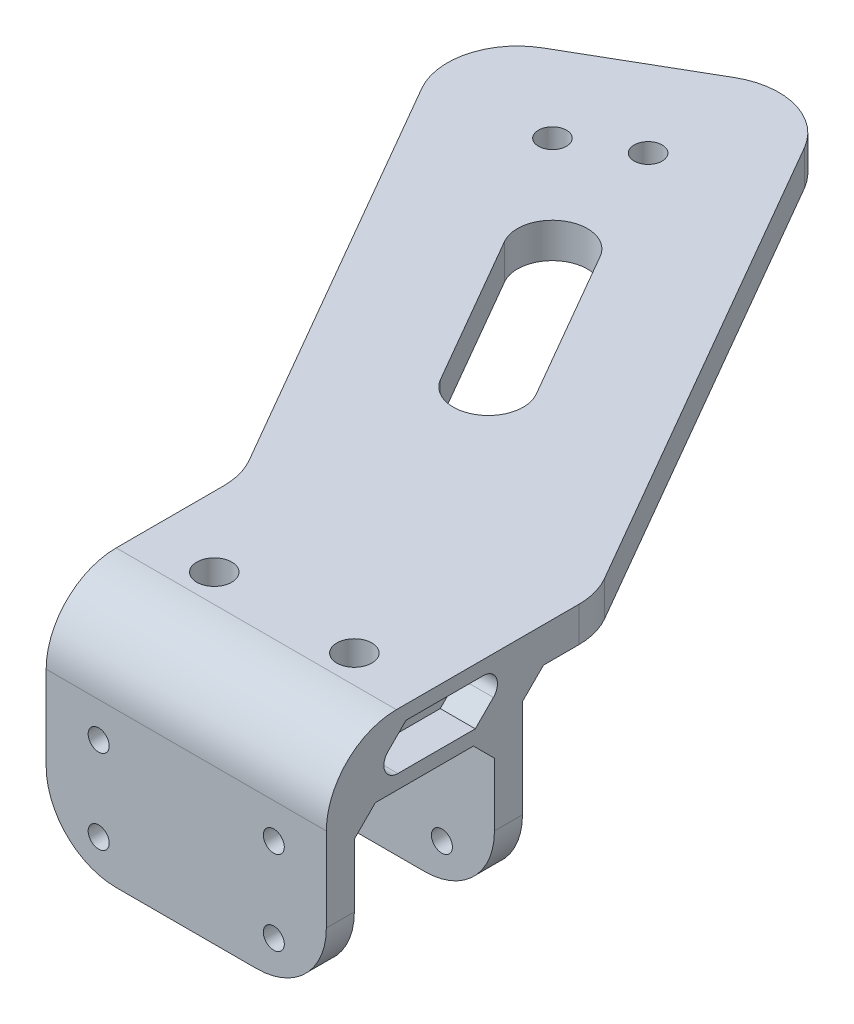
SolidWorks part; units mm, degrees
ref_plane "前视基准面" through (0, 0, 0) normal (0, 0, 1) x (1, 0, 0)
ref_plane "上视基准面" through (0, 0, 0) normal (0, 1, 0) x (1, 0, 0)
ref_plane "右视基准面" through (0, 0, 0) normal (1, 0, 0) x (0, 0, -1)
other "Configuration Table"
sketch "草图1" plane through (0, 0, 0) normal (0, 1, 0) x (1, 0, 0)
  line L1 (20, 14) -> (-20, 14)
  line L2 (20, 14) -> (20, -14)
  line L3 (20, -14) -> (-20, -14)
  line L4 (-20, 14) -> (-20, -14)
  line L5 (20, 14) -> (-20, -14) construction
  line L6 (20, -14) -> (-20, 14) construction
  point P0 (0, 0)
  dimension "D1" = 28
  dimension "D2" = 40
extrude "凸台-拉伸1" add sketch "草图1" along normal blind 10
sketch "草图2" plane through (0, 0, 0) normal (0, -1, 0) x (1, 0, 0)
  line L0 (20, 14) -> (20, -14) construction
  line L1 (-20, 14) -> (20, 14)
  line L2 (-20, 14) -> (-20, 10)
  line L3 (-20, 10) -> (20, 10)
  line L4 (20, 14) -> (20, 10)
  line L5 (-20, -14) -> (-20, 14) construction
  line L6 (-20, -10) -> (20, -10)
  line L7 (-20, -10) -> (-20, -14)
  line L8 (-20, -14) -> (20, -14)
  line L9 (20, -10) -> (20, -14)
  dimension "D1" = 4
  dimension "D2" = 4
extrude "凸台-拉伸2" add sketch "草图2" along normal blind 10
sketch "草图4" plane through (0, 0, -14) normal (0, 0, -1) x (-1, 0, 0)
  line L1 (20, 10) -> (20, -10) construction
  line L2 (-20, 10) -> (20, 10)
  line L3 (-20, 10) -> (-20, 5)
  line L4 (-20, 5) -> (20, 5)
  line L5 (20, 10) -> (20, 5)
  dimension "D1" = 5
extrude "凸台-拉伸3" add sketch "草图4" along normal blind 15
sketch "草图6" plane through (0, 0, -29) normal (0, 0, -1) x (-1, 0, 0)
  line L4 (-20, 10) -> (-20, 5)
  line L5 (-20, 5) -> (20, 5)
  line L6 (20, 5) -> (20, 10)
  line L7 (20, 10) -> (-20, 10)
  line L8 (-20, 10) -> (-20, 5)
  line L9 (-20, 5) -> (20, 5)
  line L10 (20, 5) -> (20, 10)
  line L11 (20, 10) -> (-20, 10)
  dimension "D1" = 0
extrude "凸台-拉伸4" add sketch "草图6" along normal blind 15
sketch "草图7" plane through (0, 5, 0) normal (0, -1, 0) x (1, 0, 0)
  line L0 (0, -39) -> (0, -24) construction
  line L1 (-3.15, -39) -> (-3.15, -24)
  line L2 (3.15, -39) -> (3.15, -24)
  line L3 (20, -44) -> (-20, -44) construction
  arc A0 (-3.15, -39) -> (3.15, -39) centre (0, -39) ccw
  arc A1 (3.15, -24) -> (-3.15, -24) centre (0, -24) ccw
  point P2 (0, -31.5)
  dimension "D1" = 6.3
  dimension "D2" = 15
  dimension "D3" = 5
sketch "草图8" plane through (0, 10, 0) normal (0, 1, 0) x (1, 0, 0)
  line L0 (-20, -14) -> (20, -14) construction
  line L1 (20, -14) -> (20, 44) construction
  line L2 (-20, 44) -> (-20, -14) construction
  circle A0 centre (-10, 0) radius 2.5
  circle A1 centre (10, 0) radius 2.5
  dimension "D1" = 5
  dimension "D3" = 14
  dimension "D4" = 10
  dimension "D5" = 10
  dimension "D2" = 14
extrude "切除-拉伸2" cut sketch "草图8" against normal blind 15
chamfer "倒角1" distance 3 angle 45 2 edges at (0, 0, 10) (0, 0, -10)
fillet "圆角1" radius 10 1 edges at (0, 10, 14)
chamfer "倒角2" distance 3 angle 45 1 edges at (0, 5, -14)
sketch "草图9" plane through (0, 0, -14) normal (0, 0, -1) x (-1, 0, 0)
  line L0 (20, -10) -> (-20, -10) construction
  line L1 (20, 2) -> (20, -10) construction
  line L2 (-20, 2) -> (-20, -10) construction
  circle A0 centre (-12.5, -5) radius 1.5
  circle A1 centre (12.5, -5) radius 1.5
  dimension "D1" = 5
  dimension "D2" = 5
  dimension "D3" = 7.5
  dimension "D4" = 7.5
  dimension "D5" = 3
extrude "切除-拉伸3" cut sketch "草图9" against normal through all
sketch "草图10" plane through (20, 0, 0) normal (1, 0, 0) x (0, 0, -1)
  line L0 (-2.6185, 8) -> (-8.6185, 2)
  line L1 (-8.6185, 2) -> (7.2641, 2)
  line L2 (7.2641, 2) -> (13.2641, 8)
  line L3 (13.2641, 8) -> (-2.6185, 8)
  line L4 (-7, 0) -> (7, 0) construction
  line L5 (-4, 10) -> (44, 10) construction
  line L6 (-10, -3) -> (-7, 0) construction
  dimension "D1" = 2
  dimension "D2" = 2
extrude "切除-拉伸4" cut sketch "草图10" against normal blind 5
fillet "圆角3" radius 2 2 edges at (17.5, 8, -13.2641) (17.5, 2, 8.6185)
ref_plane "基准面1" through (0, 0, 0) normal (1, 0, 0) x (0, 0, -1)
mirror "镜向1" about plane through (0, 0, 0) normal (1, 0, 0) of "切除-拉伸4"
sketch "草图11" plane through (0, -10, 0) normal (0, -1, 0) x (1, 0, 0)
  line L0 (20, 14) -> (-20, 14) construction
  line L1 (-20, -14) -> (20, -14)
  line L2 (-20, -14) -> (-20, -7)
  line L3 (-20, -7) -> (20, -7)
  line L4 (20, -14) -> (20, -7)
  line L5 (-20, 14) -> (20, 14)
  line L6 (-20, 14) -> (-20, 7)
  line L7 (-20, 7) -> (20, 7)
  line L8 (20, 14) -> (20, 7)
  dimension "D1" = 7
  dimension "D2" = 7
extrude "凸台-拉伸5" add sketch "草图11" against normal blind 3 contours L2 L1 L4 L3 | L6 L5 L8 L7
chamfer "倒角3" distance 1 angle 45 2 edges at (0, -7, -7) (0, -7, 7)
sketch "草图12" plane through (0, 0, -44) normal (0, 0, -1) x (-1, 0, 0)
  line L1 (-20, 10) -> (20, 10)
  line L2 (-20, 10) -> (-20, 5)
  line L3 (-20, 5) -> (20, 5)
  line L4 (20, 10) -> (20, 5)
extrude "凸台-拉伸6" add sketch "草图12" along normal blind 30
fillet "圆角4" radius 10 2 edges at (-20, 7.5, -74) (20, 7.5, -74)
sketch "草图13" plane through (0, 10, 0) normal (0, 1, 0) x (1, 0, 0)
  line L0 (20, -4) -> (20, 64) construction
  line L1 (-10, 74) -> (10, 74) construction
  circle A0 centre (9.14, 70) radius 2
  circle A1 centre (-0.86, 70) radius 2
  dimension "D1" = 4
  dimension "D2" = 10.86
  dimension "D3" = 10
  dimension "D4" = 4
  dimension "D5" = 4
extrude "切除-拉伸5" cut sketch "草图13" against normal blind 30
sketch "草图14" plane through (0, 10, 0) normal (0, 1, 0) x (1, 0, 0)
  line L0 (-20, 14) -> (-73.9448, 14) construction
  line L1 (-20, 14) -> (-55, 74.6218)
  line L2 (-20.359, 94.6218) -> (-55, 74.6218)
  line L3 (-20.359, 94.6218) -> (20, 24.718)
  line L4 (-20, 14) -> (-20, 7)
  line L5 (20, 14) -> (-20, 14)
  line L6 (20, 7) -> (20, 14)
  line L7 (-20, 7) -> (20, 7)
  line L8 (-20, 14) -> (-20, 7)
  line L9 (20, 14) -> (-20, 14)
  line L10 (20, 7) -> (20, 14)
  line L11 (-20, 7) -> (20, 7)
  line L12 (20, -4) -> (20, 64) construction
  line L13 (20, 24.718) -> (20, 14)
  line M13 (10, 74) -> (-10, 74)
  arc M14 (-10, 74) -> (-20, 64) centre (-10, 64) ccw
  line M15 (-20, 64) -> (-20, -4)
  line M17 (20, -4) -> (20, 64)
  dimension "D2" = 60
  dimension "D3" = 40
  dimension "D4" = 90
  dimension "D5" = 70
  dimension "D1" = 0
extrude "凸台-拉伸7" add sketch "草图14" against normal blind 5 contours L9 L3 M17 M13 M14 M15 | L3 L2 L1 M15 M14 M13 region at (-4.1679, 10, -37.9718) region at (-30.3206, 10, -62.7466)
sketch "草图15" plane through (0, 10, 0) normal (0, 1, 0) x (1, 0, 0)
  line L0 (-8.453, 74) -> (20, 24.718)
  line L1 (20, -4) -> (20, 64) construction
  line L2 (20, 24.718) -> (20, 77.5211)
  line L3 (20, 77.5211) -> (-8.453, 74)
extrude "切除-拉伸6" cut sketch "草图15" against normal blind 5
sketch "草图16" plane through (20, 0, 0) normal (1, 0, 0) x (0, 0, -1)
  line L1 (-10, -7) -> (10, -7)
  line L2 (-10, -7) -> (-10, -16.517)
  line L3 (-10, -16.517) -> (10, -16.517)
  line L4 (10, -7) -> (10, -16.517)
extrude "切除-拉伸7" cut sketch "草图16" against normal through all
sketch "草图17" plane through (0, -10, 0) normal (0, -1, 0) x (1, 0, 0)
  line L1 (-20, -10) -> (20, -10)
  line L2 (-20, -10) -> (-20, -14)
  line L3 (-20, -14) -> (20, -14)
  line L4 (20, -10) -> (20, -14)
  line L5 (-20, 14) -> (20, 14)
  line L6 (-20, 14) -> (-20, 10)
  line L7 (-20, 10) -> (20, 10)
  line L8 (20, 14) -> (20, 10)
extrude "凸台-拉伸8" add sketch "草图17" along normal blind 12
sketch "草图18" plane through (0, 0, 14) normal (0, 0, 1) x (1, 0, 0)
  line L0 (-20, -11) -> (20, -11) construction
  line L1 (-20, 0) -> (-20, -22) construction
  line L2 (20, 0) -> (20, -22) construction
  circle A0 centre (-12.5, -5) radius 1.5 construction
  circle A1 centre (-12.5, -5) radius 1.5
  circle A2 centre (12.5, -5) radius 1.5 construction
  circle A3 centre (12.5, -5) radius 1.5
  circle A4 centre (12.5, -17) radius 1.5
  circle A5 centre (-12.5, -17) radius 1.5
extrude "切除-拉伸8" cut sketch "草图18" against normal through all
sketch "草图19" plane through (0, 10, 0) normal (0, 1, 0) x (1, 0, 0)
  line L0 (-37.6795, 84.6218) -> (-1.9153, 22.6764) construction
  line L1 (-20.359, 94.6218) -> (-55, 74.6218) construction
  circle A0 centre (-30.8494, 82.7917) radius 2
  circle A1 centre (-39.5096, 77.7917) radius 2
  dimension "D1" = 4
  dimension "D2" = 5
  dimension "D3" = 5
extrude "切除-拉伸9" cut sketch "草图19" against normal through all
sketch "草图20" plane through (0, 10, 0) normal (0, 1, 0) x (1, 0, 0)
  line L0 (-37.6795, 84.6218) -> (-3.7712, 25.8908) construction
  line L1 (-20.359, 94.6218) -> (-55, 74.6218) construction
  line L2 (-25.8398, 64.1148) -> (-13.3398, 42.4642) construction
  line L3 (-21.5097, 66.6148) -> (-9.0097, 44.9642)
  line L4 (-30.1699, 61.6148) -> (-17.6699, 39.9642)
  arc A0 (-21.5097, 66.6148) -> (-30.1699, 61.6148) centre (-25.8398, 64.1148) ccw
  arc A1 (-17.6699, 39.9642) -> (-9.0097, 44.9642) centre (-13.3398, 42.4642) ccw
  point P6 (-19.5898, 53.2895)
  dimension "D1" = 25
  dimension "D2" = 10
extrude "切除-拉伸10" cut sketch "草图20" against normal through all
sketch "草图21" plane through (-46.0622, 0, -79.782) normal (-0.5, 0, -0.866) x (-0.866, 0, 0.5)
  line L1 (-29.6795, 10) -> (10.3205, 10)
  line L2 (-29.6795, 10) -> (-29.6795, 5)
  line L3 (-29.6795, 5) -> (10.3205, 5)
  line L4 (10.3205, 10) -> (10.3205, 5)
extrude "凸台-拉伸9" add sketch "草图21" along normal blind 10
fillet "圆角6" radius 10 8 edges at (-20, -22, -12) (20, -22, -12) (20, -22, 12) (-20, -22, 12) (20, 7.5, -24.718) (-20, 7.5, -14) (-60, 7.5, -83.282) (-25.359, 7.5, -103.282)
